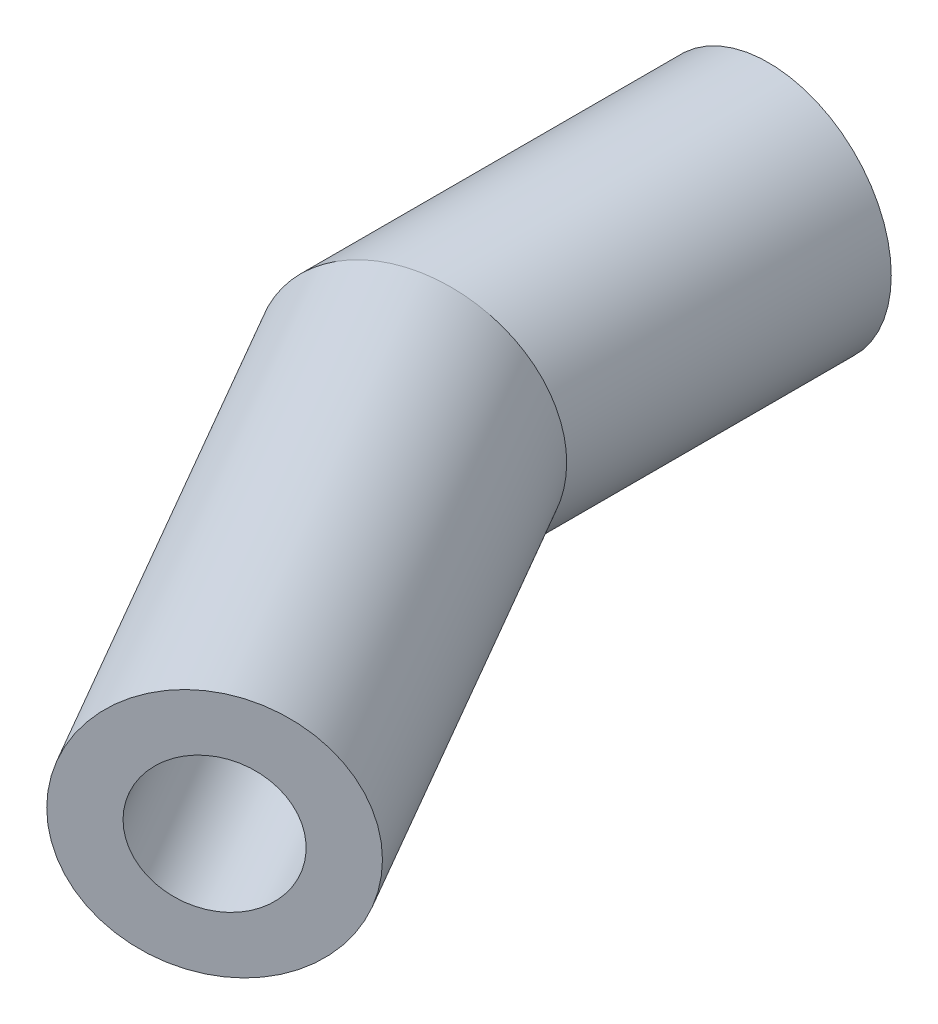
SolidWorks part; units mm, degrees
material "Silicon Rubber"
ref_plane "X-Y Datum" through (0, 0, 0) normal (0, 0, 1) x (1, 0, 0)
ref_plane "X-Z Datum" through (0, 0, 0) normal (0, 1, 0) x (1, 0, 0)
ref_plane "Y-Z Datum" through (0, 0, 0) normal (1, 0, 0) x (0, 0, -1)
sketch3d "3DSketch1"
  line L0 (0, 0, 0) -> (0, 0, 25.4)
  line L1 (0, 0, 25.4) -> (19.05, 0, 58.3956)
  line L2 (0, 0, 25.4) -> (20.0705, 0, 25.4) construction
  dimension "D1" = 25.4
  dimension "D2" = 38.1
  dimension "D3" = 300
  dimension "D4" = 61.4243
sweep "Sweep1" add path "3DSketch1" circular profile diameter 17.4625 parameters "D3"=17.4625
sweep "Cut-Sweep1" cut path "3DSketch1<2>" circular profile diameter 9.525 parameters "D3"=9.525
sketch3d "3DSketch1<2>" same geometry as "3DSketch1"
sketch3d "3DSketch3"
  line L0 (0, 0, 0) -> (0, 0, 25.4) construction
  line L1 (0, 0, 25.4) -> (0, -4.7625, 25.4)
  line L2 (0, 0, 25.4) -> (-4.7625, 0, 25.4)
  circle A0 centre (0, 0, 25.4) radius 4.7625
  circle A1 centre (0, 0, 0) radius 4.7625 construction
  circle A2 centre (0, 0, 0) radius 4.7625 construction
  point P3 (0, 0, 20.6375)
  point P9 (0, 0, -4.7625)
  point P11 (0, 0, -4.7625)
  dimension "D1" = 25.4
